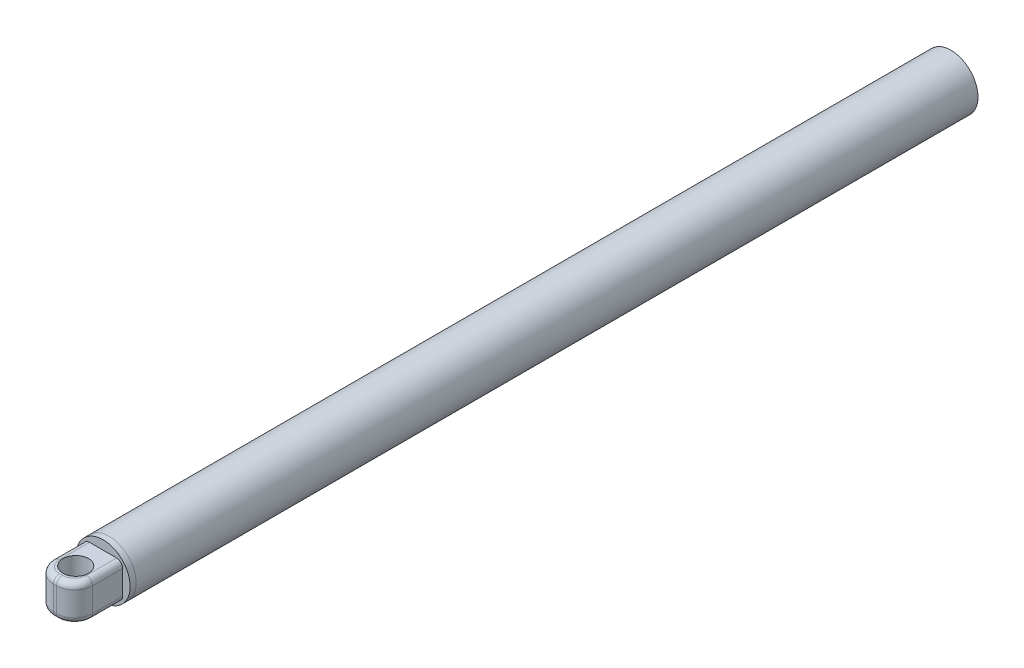
SolidWorks part; units mm, degrees
ref_plane "Front Plane" through (0, 0, 0) normal (0, 0, 1) x (1, 0, 0)
ref_plane "Top Plane" through (0, 0, 0) normal (0, 1, 0) x (1, 0, 0)
ref_plane "Right Plane" through (0, 0, 0) normal (1, 0, 0) x (0, 0, -1)
sketch "Sketch1" plane through (0, 0, 0) normal (0, 0, 1) x (1, 0, 0)
  circle A0 centre (0, 0) radius 4.5
extrude "Rod" add sketch "Sketch1" along normal blind 140
sketch "Sketch2" plane through (0, 0, 140) normal (0, 0, 1) x (1, 0, 0)
  circle A0 centre (0, 0) radius 4.5 construction
  circle A1 centre (0, 0) radius 4.5
extrude "Boss-Extrude2" add sketch "Sketch2" along normal blind 1 separate body
sketch "Sketch4" plane through (0, 0, 0) normal (0, 1, 0) x (1, 0, 0)
  line L2 (-4.5, -141) -> (-3.2554, -141) construction
  line L3 (4.5, -141) -> (3.2554, -141) construction
  line L4 (-3.2554, -141) -> (3.2554, -141)
  line L5 (3.2554, -141) -> (3.2554, -146)
  line L6 (0.2554, -149) -> (-0.2554, -149)
  line L7 (-3.2554, -146) -> (-3.2554, -141)
  line L8 (0, -149) -> (0, -141) construction
  arc A0 (3.2554, -146) -> (0.2554, -149) centre (0.2554, -146) cw
  arc A1 (-0.2554, -149) -> (-3.2554, -146) centre (-0.2554, -146) cw
  circle A2 centre (0, -145.545) radius 2.125
  dimension "D2" = 8
  dimension "D1" = 3
extrude "Boss-Extrude4" add sketch "Sketch4" along normal blind 3 and the other way blind 3
fillet "Fillet2" radius 1 10 edges at (-3.2554, -3, 143.5) (-2.3767, -3, 148.1213) (0, -3, 149) (3.2554, -3, 143.5) (-3.2554, 3, 143.5) (-2.3767, 3, 148.1213) (0, 3, 149) (3.2554, 3, 143.5) (2.3767, -3, 148.1213) (2.3767, 3, 148.1213)
ref_axis "Axis1" through (0, -3, 145.545) along (0, 1, 0)
